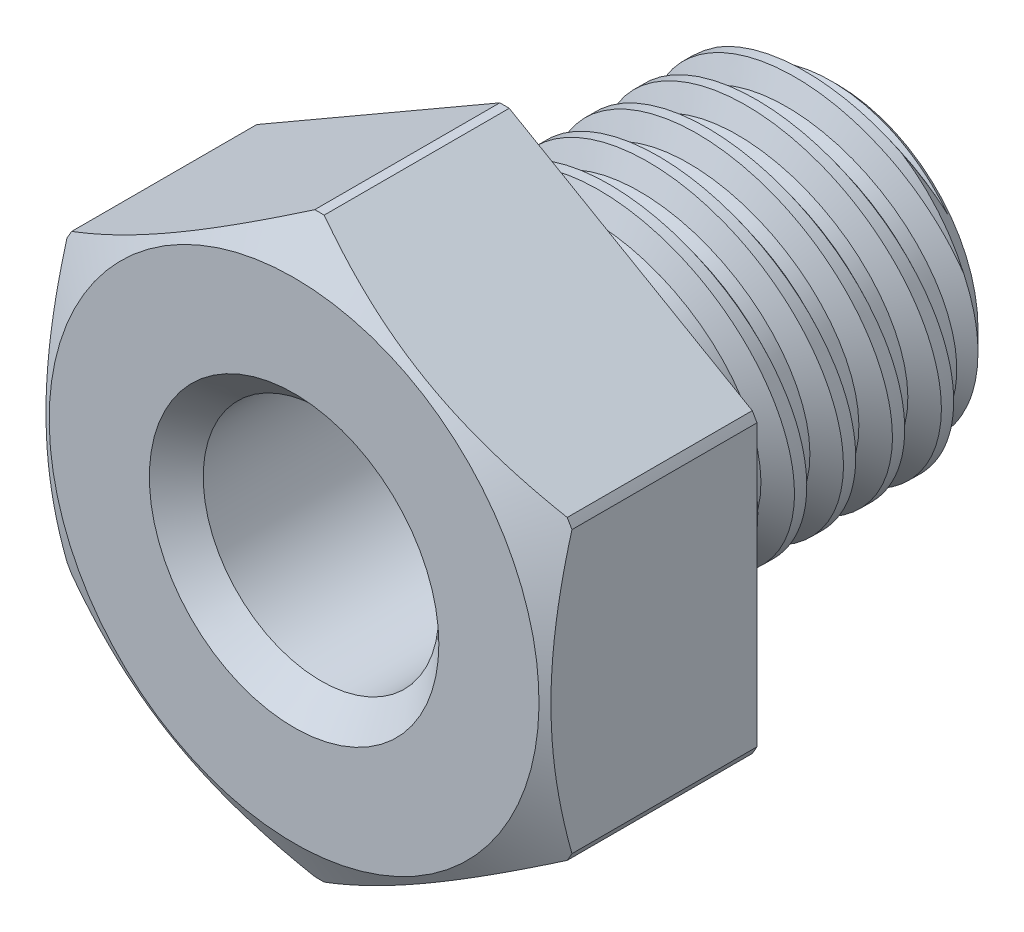
SolidWorks part; units mm, degrees
material "2024 Alloy"
ref_plane "Front" through (0, 0, 0) normal (0, 0, 1) x (1, 0, 0)
ref_plane "Top" through (0, 0, 0) normal (0, 1, 0) x (1, 0, 0)
ref_plane "Right" through (0, 0, 0) normal (1, 0, 0) x (0, 0, -1)
sketch "Sketch1" plane through (0, 0, 0) normal (1, 0, 0) x (0, 0, -1)
  line L0 (-19.05, 0) -> (-28.9719, 0) construction
  line L1 (-19.05, 0) -> (-19.05, 11.9063) construction
  line L2 (-19.05, 0) -> (-28.9719, 0) construction
  line L3 (-19.05, -7.9375) -> (19.05, -7.9375) construction
  line L4 (-19.05, 0) -> (19.05, 0)
  line L5 (-19.05, 0) -> (-19.05, 7.9375)
  line L6 (-19.05, 7.9375) -> (19.05, 7.9375)
  line L7 (19.05, 0) -> (19.05, 7.9375)
  dimension "Screw Dia" = 15.875
  dimension "Screw Length" = 38.1
  dimension "Head Height" = 9.9219
  dimension "Head Width" = 23.8125
revolve "Revolve1" add sketch "Sketch1" angle 360 about L0
sketch "Sketch2" plane through (0, 0, 0) normal (1, 0, 0) x (0, 0, -1)
  line L0 (-19.05, 7.9375) -> (-19.05, -7.9375) construction
  line L1 (-19.05, -7.9375) -> (-16.7409, -7.9375) construction
  line L2 (-16.7409, -7.9375) -> (-19.05, 7.9375) construction
  line L3 (-19.05, 7.9375) -> (-18.7644, 7.979) construction
  line L4 (-16.765, 8.2699) -> (-18.7644, 7.979)
  line L5 (-18.7644, 7.979) -> (-17.8704, 6.8461)
  line L6 (-17.8704, 6.8461) -> (-17.2991, 6.9292)
  line L7 (-17.2991, 6.9292) -> (-16.765, 8.2699)
  line L8 (-17.5848, 6.8876) -> (-17.7647, 8.1245) construction
  line L9 (-19.05, 0) -> (-19.05, 7.9375) construction
  line L10 (-19.05, 7.9375) -> (-17.7375, 7.9375) construction
  line L11 (-17.7375, 7.9375) -> (-15.4284, -7.9375) construction
  line L12 (-15.4284, -7.9375) -> (-16.7409, -7.9375) construction
  line L13 (-19.05, -7.9375) -> (19.05, -7.9375) construction
  line L14 (-19.05, -0.3588) -> (-14.1158, 0.3588) construction
  line L15 (-19.05, 7.9375) -> (19.05, 7.9375) construction
  point P17 (-16.5829, 0)
  dimension "D1" = 2.3091
  dimension "Thread Pitch" = 2.3091
  dimension "D3" = 0.5773
  dimension "D4" = 0.2886
  dimension "D5" = 60
revolve "Cut-Revolve1" cut sketch "Sketch2" angle 360 about L14
sketch "Sketch3" plane through (0, 0, 0) normal (1, 0, 0) x (0, 0, -1)
  line L0 (16.7095, 7.9375) -> (19.05, 6.8461)
  line L1 (19.05, 6.8461) -> (19.05, 7.9375)
  line L2 (19.05, 7.9375) -> (16.7095, 7.9375)
  line L3 (-19.05, 7.9375) -> (19.05, 7.9375) construction
  line L4 (19.05, 0) -> (19.05, 7.9375) construction
  line L5 (-17.8704, 6.8461) -> (19.05, 6.8461) construction
  line L6 (16.7095, 7.9375) -> (16.7095, -7.9375) construction
  line L7 (-19.05, -7.9375) -> (19.05, -7.9375) construction
  line L8 (0, 0) -> (16.7095, 0) construction
  dimension "D1" = 25
  dimension "D2" = 15.875
revolve "Cut-Revolve2" cut sketch "Sketch3" angle 360 about L8
pattern_linear "LPattern1" count 2 spacing 2.3091 along (0, 0, 1) count 17 spacing 2.3091 along (0, 0, -1) of "Cut-Revolve1"
sketch "Sketch5" plane through (0, 0, 19.05) normal (0, 0, 1) x (1, 0, 0)
  line L1 (0, 13.7482) -> (-11.9062, 6.8741)
  line L2 (-11.9062, 6.8741) -> (-11.9062, -6.8741)
  line L3 (-11.9062, -6.8741) -> (0, -13.7482)
  line L4 (0, -13.7482) -> (11.9062, -6.8741)
  line L5 (11.9062, -6.8741) -> (11.9062, 6.8741)
  line L6 (11.9062, 6.8741) -> (0, 13.7482)
  circle A0 centre (0, 0) radius 11.9062 construction
  dimension "D1" = 23.8125
extrude "Extrude1" add sketch "Sketch5" along normal up to vertex (9.9219 mm away) up to point (0, 0, 28.9719)
sketch "Sketch6" plane through (0, 0, 0) normal (1, 0, 0) x (0, 0, -1)
  line L0 (-28.9719, 11.5491) -> (-27.7756, 13.6212)
  line L1 (-27.7756, 13.6212) -> (-19.05, 13.6212)
  line L2 (-19.05, 13.6212) -> (-19.05, 14.1292)
  line L3 (-19.05, 14.1292) -> (-28.9719, 14.1292)
  line L4 (-28.9719, 14.1292) -> (-28.9719, 11.5491)
  line L5 (-28.9719, 6.8741) -> (-28.9719, 13.7482) construction
  line L6 (-28.9719, 13.7482) -> (-19.05, 13.7482) construction
  line L7 (-19.05, 6.8741) -> (-19.05, 13.7482) construction
  line L8 (0, 0) -> (-27.7756, 0) construction
  line L9 (-19.05, 0) -> (-28.9719, 0) construction
  line L10 (-27.7756, 0) -> (-27.7756, 13.6212) construction
  line L11 (-24.0109, 14.1292) -> (-24.0109, 0) construction
  dimension "D1" = 30
  dimension "D2" = 0.127
  dimension "D3" = 0.508
  dimension "D4" = 23.0981
  dimension "D5" = 9.9219
  dimension "D6" = 38.1
revolve "Cut-Revolve3" cut sketch "Sketch6" angle 360 about L8
ref_plane "Plane1" through (0, 0, 3.175) normal (0, 0, -1) x (-1, 0, 0)
sketch "Sketch7" plane through (0, 0, 3.175) normal (0, 0, -1) x (-1, 0, 0)
  circle A0 centre (0, 0) radius 8.8043
extrude "Cut-Extrude1" cut sketch "Sketch7" along normal up to next
sketch "Sketch8" plane through (0, 0, 0) normal (1, 0, 0) x (0, 0, -1)
  line L0 (-5.715, 8.9936) -> (-3.175, 6.4536)
  line L1 (-3.175, 5.0758) -> (-3.175, 7.6058) construction
  line L2 (-3.175, 6.4536) -> (-3.175, 8.9936)
  line L3 (-3.175, 8.9936) -> (-5.715, 8.9936)
  line L4 (0, 0) -> (-24.2632, 0) construction
  dimension "D1" = 45
  dimension "D2" = 2.54
revolve "Cut-Revolve4" cut sketch "Sketch8" angle 360 about L4
sketch "Sketch9" plane through (0, 0, 28.9719) normal (0, 0, 1) x (1, 0, 0)
  circle A0 centre (0, 0) radius 5.5562
  dimension "D1" = 11.1125
extrude "Cut-Extrude2" cut sketch "Sketch9" against normal through all
chamfer "Chamfer1" distance 1.27 angle 45 2 edges at (5.5562, 0, 28.9719) (5.5562, 0, 3.175)
equation "\"D3@Sketch2\"=\"Thread Pitch@Sketch2\"/4"
equation "\"D4@Sketch2\"=\"Thread Pitch@Sketch2\"/8"
equation "\"D1@Sketch2\"=\"Thread Pitch@Sketch2\""
equation "\"D3@LPattern1\"=\"Thread Pitch@Sketch2\""
equation "\"D4@LPattern1\"=\"Thread Pitch@Sketch2\""
equation "\"D4@Sketch6\"=\"Head Width@Sketch1\"*.97"
equation "\"D2@LPattern1\"=\"Screw Length@Sketch1\"/\"Thread Pitch@Sketch2\""
